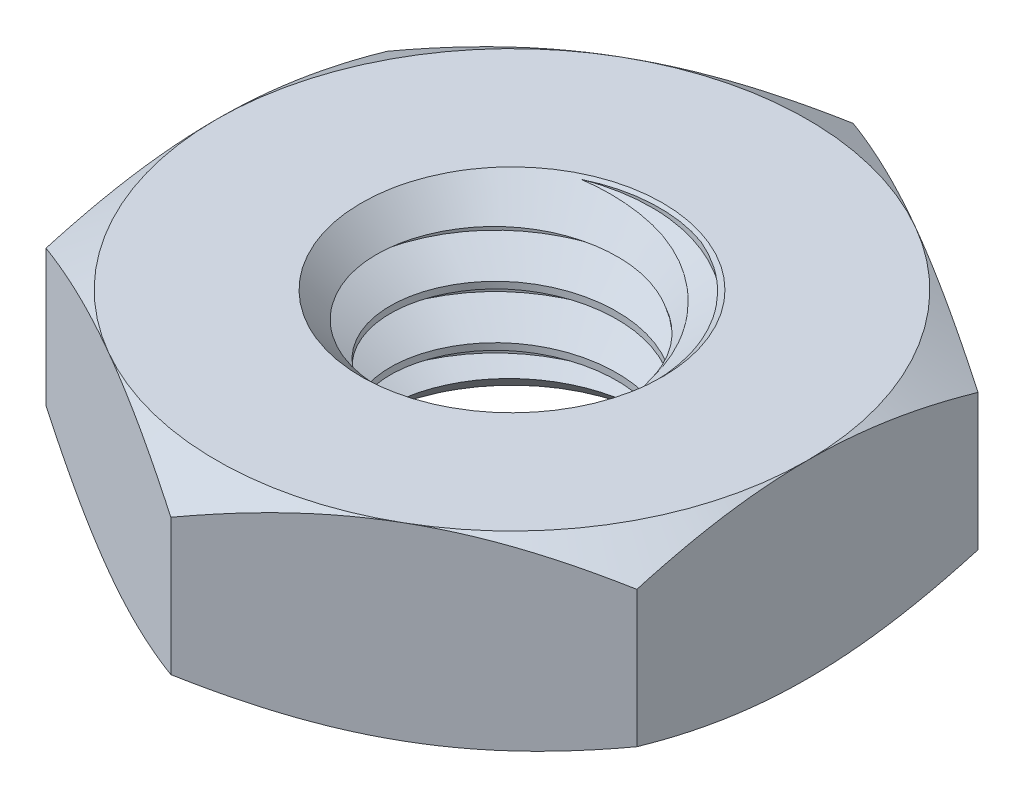
SolidWorks part; units mm, degrees
ref_plane "Front Plane" through (0, 0, 0) normal (0, 0, 1) x (1, 0, 0)
ref_plane "Top Plane" through (0, 0, 0) normal (0, 1, 0) x (1, 0, 0)
ref_plane "Right Plane" through (0, 0, 0) normal (1, 0, 0) x (0, 0, -1)
sketch "Sketch8" plane through (0, 0, 0) normal (0, 1, 0) x (1, 0, 0)
  line L0 (-2.5, 0) -> (2.5, 0) construction
  line L1 (0, 1.25) -> (0, -1.25) construction
  line L2 (0, 1.25) -> (-0.45, 1.25) construction
  line L3 (2.5, -0.8) -> (2.5, 0.8) construction
  point P4 (0, 0)
  point P8 (0, 0)
  point P11 (2.5, 0)
  dimension "Hex Size" = 5
  dimension "Thread Size" = 2.5
  dimension "Pitch" = 0.45
  dimension "Hex Height" = 1.6
sketch "Sketch1" plane through (0, 0, 0) normal (0, 1, 0) x (1, 0, 0)
  line L1 (-2.5, 1.4434) -> (-2.5, -1.4434)
  line L2 (-2.5, -1.4434) -> (0, -2.8868)
  line L3 (0, -2.8868) -> (2.5, -1.4434)
  line L4 (2.5, -1.4434) -> (2.5, 1.4434)
  line L5 (2.5, 1.4434) -> (0, 2.8868)
  line L6 (0, 2.8868) -> (-2.5, 1.4434)
  circle A0 centre (0, 0) radius 2.5 construction
  circle A1 centre (0, 0) radius 1.25
  dimension "Thread Size" = 2.5
  dimension "Hex" = 5
extrude "Boss-Extrude1" add sketch "Sketch1" along normal mid plane 1.6
sketch "Sketch5" plane through (0, 0.8, 0) normal (0, 1, 0) x (1, 0, 0)
  line L0 (-2.5, 1.4434) -> (-2.5, -1.4434) construction
  circle A1 centre (0, 0) radius 2.5
  circle A2 centre (0, 0) radius 1.25 construction
extrude "Cut-Extrude2" cut sketch "Sketch5" against normal through all draft 60 flip side to cut
mirror "Mirror1" about plane through (0, 0, 0) normal (0, 1, 0) of "Cut-Extrude2"
sketch "Sketch2" plane through (0, 0.8, 0) normal (0, 1, 0) x (1, 0, 0)
  circle A0 centre (0, 0) radius 1.25 construction
  circle A1 centre (0, 0) radius 1.25
sketch "Sketch7" plane through (0, 0, 0) normal (0, 1, 0) x (1, 0, 0)
  line L0 (0, 0) -> (0.625, -1.0825)
  line L1 (0, 0) -> (-1.25, 0) construction
  circle A0 centre (0, 0) radius 1.25 construction
  dimension "D1" = 120
curve "Helix/Spiral1" pitch 0.45 height 2.05 radius 1.25 centre (0, 0.8, 0) axis (0, -1, 0) start towards (0, 0, 1) parameters "Pitch"=0.45
sketch "Sketch3" plane through (0, 0, 0) normal (1, 0, 0) x (0, 0, -1)
  line L0 (1.2987, 1.2219) -> (1.2987, 0.7719) construction
  line L1 (1.2987, 0.7719) -> (0.909, 0.9969) construction
  line L2 (0.909, 0.9969) -> (1.2987, 1.2219) construction
  line L3 (1.2987, 0.9969) -> (1.25, 0.9969) construction
  line L4 (1.25, 0.9969) -> (0.9577, 0.9969) construction
  line L5 (0.9577, 0.9969) -> (0.909, 0.9969) construction
  line L7 (0.9577, 0.9688) -> (0.9577, 1.025)
  line L8 (1.25, 0.8) -> (1.25, 1.1937) construction
  line L9 (1.2744, 0.7859) -> (1.2744, 1.2078)
  line L10 (1.2744, 1.2078) -> (0.9577, 1.025)
  line L11 (1.2744, 0.7859) -> (0.9577, 0.9688)
  point P9 (0.9577, 0.9969)
  point P12 (1.25, 0.9969)
  point P16 (1.2744, 0.9969)
  dimension "D1" = 0.45
  dimension "D2" = 0.0563
sweep "Sweep1" add profiles "Sketch3" path "Helix/Spiral1"
sketch "Sketch4" plane through (0, 0.8, 0) normal (0, 1, 0) x (1, 0, 0)
  circle A2 centre (0, 0) radius 1.2744
extrude "Cut-Extrude1" cut sketch "Sketch4" along normal through all and the other way through all draft 45
mirror "Mirror2" about plane through (0, 0, 0) normal (0, 1, 0) of "Cut-Extrude1"
equation "\"D3@Helix/Spiral1\"=\"Hex Height@Sketch8\"+\"Pitch@Sketch8\""
equation "\"Height@Boss-Extrude1\"=\"Hex Height@Sketch8\""
equation "\"Thread Size@Sketch1\"=\"Thread Size@Sketch8\""
equation "\"Hex@Sketch1\"=\"Hex Size@Sketch8\""
equation "\"Pitch@Helix/Spiral1\"=\"Pitch@Sketch8\""
equation "\"D1@Sketch3\"=\"Pitch@Sketch8\""
equation "\"D2@Sketch3\"=\"D1@Sketch3\"/8"
